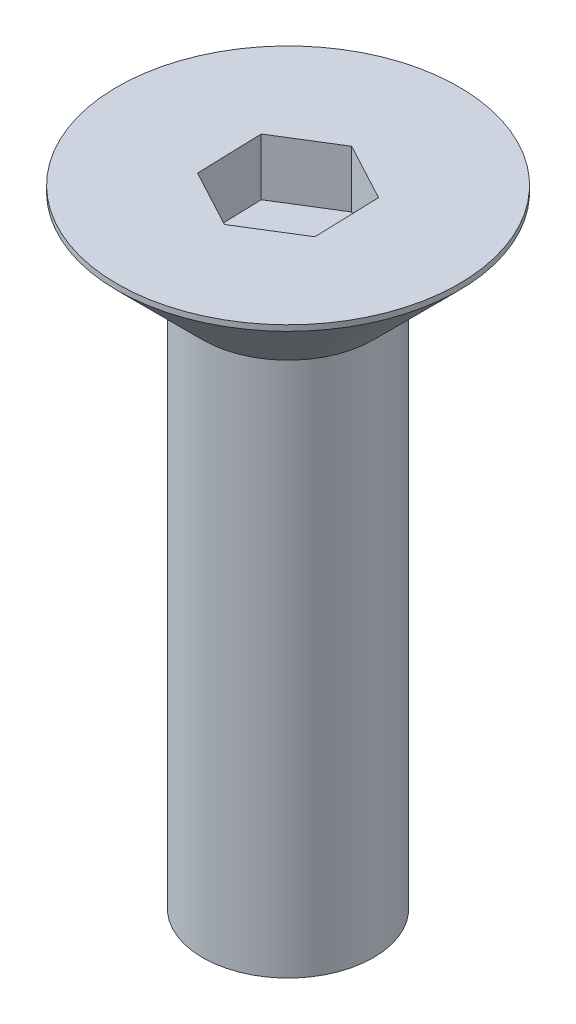
SolidWorks part; units mm, degrees
ref_plane "前视基准面" through (0, 0, 0) normal (0, 0, 1) x (1, 0, 0)
ref_plane "上视基准面" through (0, 0, 0) normal (0, 1, 0) x (1, 0, 0)
ref_plane "右视基准面" through (0, 0, 0) normal (1, 0, 0) x (0, 0, -1)
sketch "草图1" plane through (0, 0, 0) normal (0, 1, 0) x (1, 0, 0)
  circle A0 centre (0, 0) radius 1.5
  dimension "D1" = 3
extrude "凸台-拉伸1" add sketch "草图1" along normal blind 8
sketch "草图2" plane through (0, 8, 0) normal (0, 1, 0) x (1, 0, 0)
  circle A0 centre (0, 0) radius 3
  dimension "D1" = 6
extrude "凸台-拉伸2" add sketch "草图2" along normal blind 3
chamfer "倒角1" distance 2.9 angle 45 1 edges at (0, 8, 3)
sketch "草图3" plane through (0, 11, 0) normal (0, 1, 0) x (1, 0, 0)
  line L1 (1.0175, -0.5459) -> (0.9815, 0.6083)
  line L2 (0.9815, 0.6083) -> (-0.036, 1.1541)
  line L3 (-0.036, 1.1541) -> (-1.0175, 0.5459)
  line L4 (-1.0175, 0.5459) -> (-0.9815, -0.6083)
  line L5 (-0.9815, -0.6083) -> (0.036, -1.1541)
  line L6 (0.036, -1.1541) -> (1.0175, -0.5459)
  circle A0 centre (0, 0) radius 1 construction
  point P1 (0.9995, 0.0312)
  dimension "D1" = 2
extrude "切除-拉伸1" cut sketch "草图3" against normal blind 1
